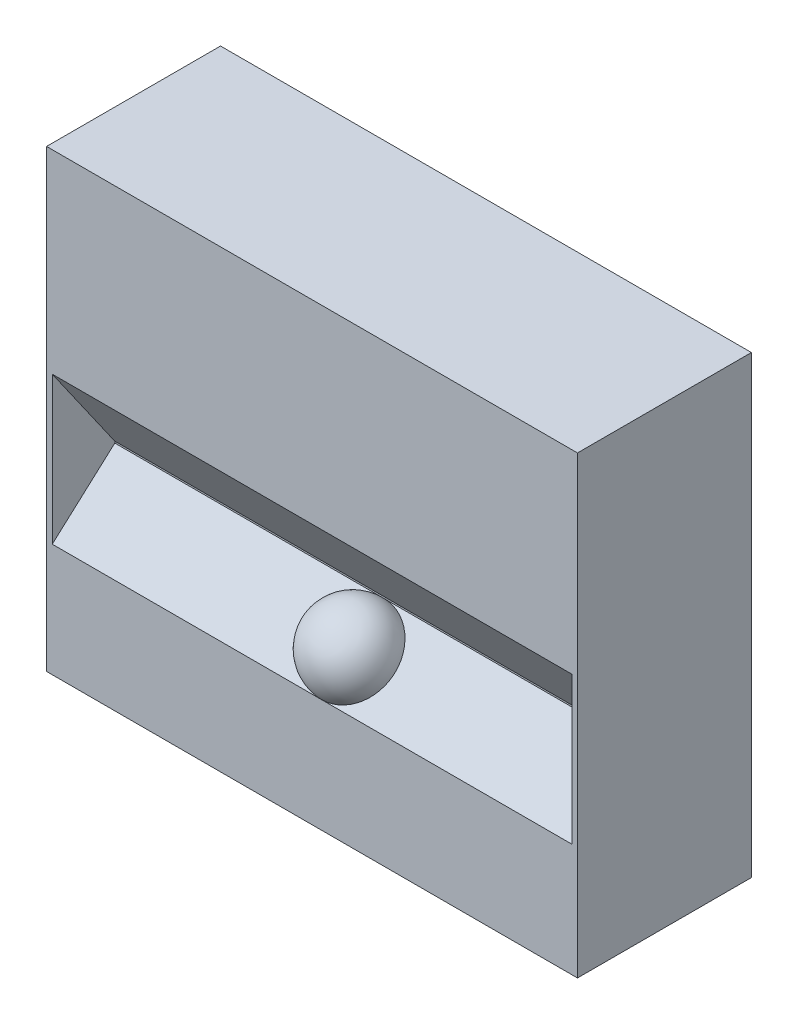
SolidWorks part; units mm, degrees
ref_plane "Plan de face" through (0, 0, 0) normal (0, 0, 1) x (1, 0, 0)
ref_plane "Plan de dessus" through (0, 0, 0) normal (0, 1, 0) x (1, 0, 0)
ref_plane "Plan de droite" through (0, 0, 0) normal (1, 0, 0) x (0, 0, -1)
sketch "Esquisse1" plane through (0, 0, 0) normal (0, 0, 1) x (1, 0, 0)
  line L1 (-266.153, 210.7045) -> (200.847, 210.7045)
  line L2 (-266.153, 210.7045) -> (-266.153, -189.2955)
  line L3 (-266.153, -189.2955) -> (200.847, -189.2955)
  line L4 (200.847, 210.7045) -> (200.847, -189.2955)
  dimension "D1" = 467
  dimension "D2" = 400
extrude "Boss.-Extru.1" add sketch "Esquisse1" along normal blind 153
sketch "Esquisse2" plane through (0, 0, 153) normal (0, 0, 1) x (1, 0, 0)
  line L0 (200.847, -189.2955) -> (200.847, 210.7045) construction
  line L1 (-261.153, 39.7045) -> (195.847, 39.7045)
  line L2 (-261.153, 39.7045) -> (-261.153, -90.2955)
  line L3 (-261.153, -90.2955) -> (195.847, -90.2955)
  line L4 (195.847, 39.7045) -> (195.847, -90.2955)
  line L5 (-266.153, 210.7045) -> (-266.153, -189.2955) construction
  line L7 (200.847, 210.7045) -> (-266.153, 210.7045) construction
  dimension "D1" = 5
  dimension "D2" = 5
  dimension "D3" = 301
  dimension "D4" = 130
extrude "Enlèv. mat.-Extru.1" cut sketch "Esquisse2" against normal blind 55
chamfer "Chanfrein2" distance 55 angle 55 1 edges at (-32.653, 39.7045, 98) first distance on face at (-32.653, 39.7045, 125.5)
chamfer "Chanfrein3" distance 50 angle 48 1 edges at (-32.653, -90.2955, 98) first distance on face at (-32.653, -64.5696, 98)
sketch "Esquisse3" plane through (0, 26.4778, 23.8407) normal (0, 0.7431, 0.6691) x (1, 0, 0)
  line L1 (-24.478, -173.801) -> (-24.478, -99.7912) construction
  line L3 (195.847, -173.801) -> (-261.153, -173.801) construction
  line L4 (-261.153, -99.7912) -> (195.847, -99.7912) construction
  line L5 (-24.478, -173.801) -> (-24.478, -99.7912)
  arc A1 (-24.478, -173.801) -> (-24.478, -99.7912) centre (-24.478, -136.7961) cw
revolve "Révolution1" add sketch "Esquisse3" angle 182 about L1
